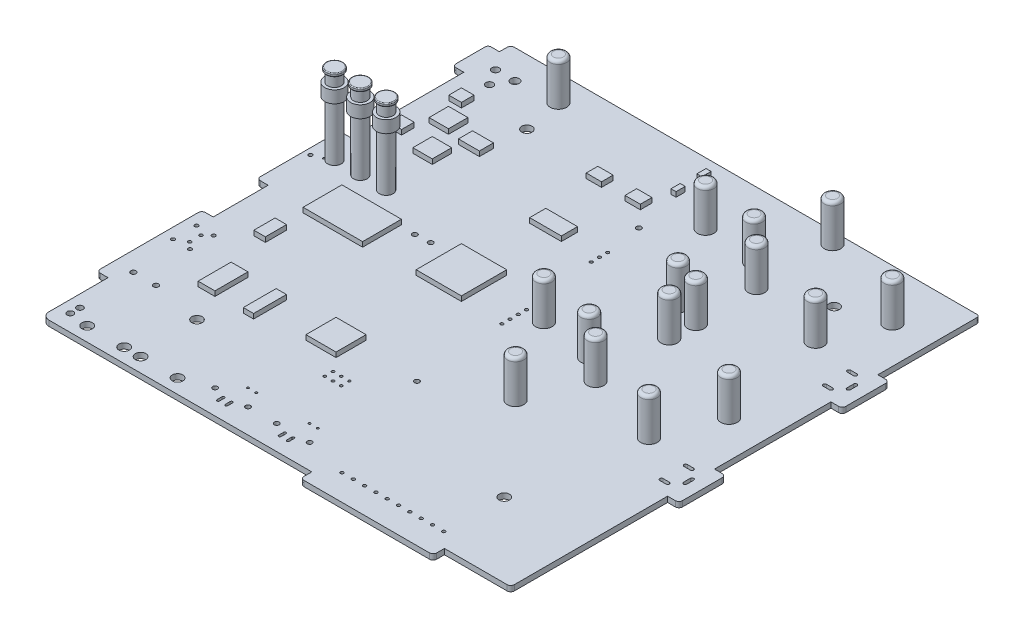
SolidWorks part; units mm, degrees
ref_plane "Front Plane" through (0, 0, 0) normal (0, 0, 1) x (1, 0, 0)
ref_plane "Top Plane" through (0, 0, 0) normal (0, 1, 0) x (1, 0, 0)
ref_plane "Right Plane" through (0, 0, 0) normal (1, 0, 0) x (0, 0, -1)
sketch "Sketch2"
sketch "Sketch3" plane through (0, 0, 0) normal (0, 1, 0) x (1, 0, 0)
  line L0 (-2.382, 130.5) -> (0, 130.5) construction
  line L1 (0, 130.5) -> (0, 95.5) construction
  line L2 (0, 95.5) -> (-2.382, 95.5) construction
  line L3 (-3.5, 94.382) -> (-3.5, 71.118) construction
  line L4 (-2.382, 70) -> (0, 70) construction
  line L5 (0, 70) -> (0, 53) construction
  line L6 (0, 53) -> (-2.382, 53) construction
  line L7 (-3.5, 51.882) -> (-3.5, 21.618) construction
  line L8 (-2.382, 20.5) -> (0, 20.5) construction
  line L9 (0, 20.5) -> (0, 2.2361) construction
  line L10 (83.5, 0) -> (2.2361, 0) construction
  line L11 (83.5, -2.382) -> (83.5, 0) construction
  line L12 (123.382, -3.5) -> (84.618, -3.5) construction
  line L13 (124.5, 0) -> (124.5, -2.382) construction
  line L14 (143.882, 0) -> (124.5, 0) construction
  line L15 (145, 48.5) -> (145, 1.118) construction
  line L16 (147.382, 48.5) -> (145, 48.5) construction
  line L17 (148.5, 61.882) -> (148.5, 49.618) construction
  line L18 (145, 63) -> (147.382, 63) construction
  line L19 (145, 99) -> (145, 63) construction
  line L20 (147.382, 99) -> (145, 99) construction
  line L21 (148.5, 112.382) -> (148.5, 100.118) construction
  line L22 (145, 113.5) -> (147.382, 113.5) construction
  line L23 (145, 144.0986) -> (145, 113.5) construction
  line L24 (144.0986, 145) -> (1.118, 145) construction
  line L25 (0, 143.882) -> (0, 141.5) construction
  line L26 (0, 141.5) -> (-2.5986, 141.5) construction
  line L27 (-3.5, 140.5986) -> (-3.5, 131.618) construction
  line L28 (-2.382, 130.5) -> (0, 130.5)
  line L29 (0, 130.5) -> (0, 95.5)
  line L30 (0, 95.5) -> (-2.382, 95.5)
  line L31 (-3.5, 94.382) -> (-3.5, 71.118)
  line L32 (-2.382, 70) -> (0, 70)
  line L33 (0, 70) -> (0, 53)
  line L34 (0, 53) -> (-2.382, 53)
  line L35 (-3.5, 51.882) -> (-3.5, 21.618)
  line L36 (-2.382, 20.5) -> (0, 20.5)
  line L37 (0, 20.5) -> (0, 2.2361)
  line L38 (83.5, 0) -> (2.2361, 0)
  line L39 (83.5, -2.382) -> (83.5, 0)
  line L40 (123.382, -3.5) -> (84.618, -3.5)
  line L41 (124.5, 0) -> (124.5, -2.382)
  line L42 (143.882, 0) -> (124.5, 0)
  line L43 (145, 48.5) -> (145, 1.118)
  line L44 (147.382, 48.5) -> (145, 48.5)
  line L45 (148.5, 61.882) -> (148.5, 49.618)
  line L46 (145, 63) -> (147.382, 63)
  line L47 (145, 99) -> (145, 63)
  line L48 (147.382, 99) -> (145, 99)
  line L49 (148.5, 112.382) -> (148.5, 100.118)
  line L50 (145, 113.5) -> (147.382, 113.5)
  line L51 (145, 144.0986) -> (145, 113.5)
  line L52 (144.0986, 145) -> (1.118, 145)
  line L53 (0, 143.882) -> (0, 141.5)
  line L54 (0, 141.5) -> (-2.5986, 141.5)
  line L55 (-3.5, 140.5986) -> (-3.5, 131.618)
  arc A0 (-3.5, 131.618) -> (-2.382, 130.5) centre (-2.382, 131.618) ccw construction
  arc A1 (-2.382, 95.5) -> (-3.5, 94.382) centre (-2.382, 94.382) ccw construction
  arc A2 (-3.5, 71.118) -> (-2.382, 70) centre (-2.382, 71.118) ccw construction
  arc A3 (-2.382, 53) -> (-3.5, 51.882) centre (-2.382, 51.882) ccw construction
  arc A4 (-3.5, 21.618) -> (-2.382, 20.5) centre (-2.382, 21.618) ccw construction
  arc A5 (0, 2.2361) -> (2.2361, 0) centre (2.2361, 2.2361) ccw construction
  arc A6 (83.5, -2.382) -> (84.618, -3.5) centre (84.618, -2.382) ccw construction
  arc A7 (123.382, -3.5) -> (124.5, -2.382) centre (123.382, -2.382) ccw construction
  arc A8 (143.882, 0) -> (145, 1.118) centre (143.882, 1.118) ccw construction
  arc A9 (147.382, 48.5) -> (148.5, 49.618) centre (147.382, 49.618) ccw construction
  arc A10 (148.5, 61.882) -> (147.382, 63) centre (147.382, 61.882) ccw construction
  arc A11 (147.382, 99) -> (148.5, 100.118) centre (147.382, 100.118) ccw construction
  arc A12 (148.5, 112.382) -> (147.382, 113.5) centre (147.382, 112.382) ccw construction
  arc A13 (145, 144.0986) -> (144.0986, 145) centre (144.0986, 144.0986) ccw construction
  arc A14 (1.118, 145) -> (0, 143.882) centre (1.118, 143.882) ccw construction
  arc A15 (-2.5986, 141.5) -> (-3.5, 140.5986) centre (-2.5986, 140.5986) ccw construction
  arc A16 (-3.5, 131.618) -> (-2.382, 130.5) centre (-2.382, 131.618) ccw
  arc A17 (-2.382, 95.5) -> (-3.5, 94.382) centre (-2.382, 94.382) ccw
  arc A18 (-3.5, 71.118) -> (-2.382, 70) centre (-2.382, 71.118) ccw
  arc A19 (-2.382, 53) -> (-3.5, 51.882) centre (-2.382, 51.882) ccw
  arc A20 (-3.5, 21.618) -> (-2.382, 20.5) centre (-2.382, 21.618) ccw
  arc A21 (0, 2.2361) -> (2.2361, 0) centre (2.2361, 2.2361) ccw
  arc A22 (83.5, -2.382) -> (84.618, -3.5) centre (84.618, -2.382) ccw
  arc A23 (123.382, -3.5) -> (124.5, -2.382) centre (123.382, -2.382) ccw
  arc A24 (143.882, 0) -> (145, 1.118) centre (143.882, 1.118) ccw
  arc A25 (147.382, 48.5) -> (148.5, 49.618) centre (147.382, 49.618) ccw
  arc A26 (148.5, 61.882) -> (147.382, 63) centre (147.382, 61.882) ccw
  arc A27 (147.382, 99) -> (148.5, 100.118) centre (147.382, 100.118) ccw
  arc A28 (148.5, 112.382) -> (147.382, 113.5) centre (147.382, 112.382) ccw
  arc A29 (145, 144.0986) -> (144.0986, 145) centre (144.0986, 144.0986) ccw
  arc A30 (1.118, 145) -> (0, 143.882) centre (1.118, 143.882) ccw
  arc A31 (-2.5986, 141.5) -> (-3.5, 140.5986) centre (-2.5986, 140.5986) ccw
  circle A32 centre (40.5, 79.75) radius 0.762 construction
  circle A33 centre (35.875, 79.5) radius 0.762 construction
  circle A34 centre (25, 23) radius 1.6 construction
  circle A35 centre (25, 125) radius 1.6 construction
  circle A36 centre (120, 125) radius 1.6 construction
  circle A37 centre (120, 23) radius 1.6 construction
  circle A38 centre (75.5, 40.5) radius 0.762 construction
  circle A39 centre (55.977, 35.0066) radius 0.5 construction
  circle A40 centre (65.0002, 30.1361) radius 0.381 construction
  circle A41 centre (75.275, 7.55) radius 0.75 construction
  circle A42 centre (72.735, 12.63) radius 0.3375 construction
  circle A43 centre (70.195, 12.63) radius 0.3375 construction
  circle A44 centre (65.115, 7.55) radius 0.75 construction
  circle A45 centre (53.685, 12.63) radius 0.3375 construction
  circle A46 centre (51.145, 12.63) radius 0.3375 construction
  circle A47 centre (56.225, 7.55) radius 0.75 construction
  circle A48 centre (46.065, 7.55) radius 0.75 construction
  circle A49 centre (37.592, 4.4) radius 1.6256 construction
  circle A50 centre (26.162, 4.4) radius 1.6256 construction
  circle A51 centre (21.082, 4.4) radius 1.6256 construction
  circle A52 centre (9.652, 4.4) radius 1.6256 construction
  circle A53 centre (3.7135, 5.121) radius 0.9652 construction
  circle A54 centre (3.7135, 8.0928) radius 0.9652 construction
  circle A55 centre (9.4624, 25.8572) radius 0.8 construction
  circle A56 centre (2.4624, 25.8572) radius 0.8 construction
  circle A57 centre (5.0334, 40.8053) radius 0.5625 construction
  circle A58 centre (3.0334, 42.7053) radius 0.5 construction
  circle A59 centre (-0.2666, 40.8053) radius 0.5625 construction
  circle A60 centre (5.0334, 48.1053) radius 0.5625 construction
  circle A61 centre (3.0334, 46.2053) radius 0.5 construction
  circle A62 centre (-0.2666, 48.1053) radius 0.5625 construction
  circle A63 centre (-1.5618, 84.65) radius 0.575 construction
  circle A64 centre (1.4382, 85.825) radius 0.3187 construction
  circle A65 centre (1.4382, 90.675) radius 0.3187 construction
  circle A66 centre (-1.5618, 91.85) radius 0.575 construction
  circle A67 centre (7.3, 131.15) radius 1.125 construction
  circle A68 centre (10.25, 136.05) radius 1.3125 construction
  circle A69 centre (4.25, 136.05) radius 1.125 construction
  circle A70 centre (40.5, 79.75) radius 0.762
  circle A71 centre (35.875, 79.5) radius 0.762
  circle A72 centre (25, 23) radius 1.6
  circle A73 centre (25, 125) radius 1.6
  circle A74 centre (120, 125) radius 1.6
  circle A75 centre (120, 23) radius 1.6
  circle A76 centre (75.5, 40.5) radius 0.762
  circle A77 centre (55.977, 35.0066) radius 0.5
  circle A78 centre (65.0002, 30.1361) radius 0.381
  circle A79 centre (75.275, 7.55) radius 0.75
  circle A80 centre (72.735, 12.63) radius 0.3375
  circle A81 centre (70.195, 12.63) radius 0.3375
  circle A82 centre (65.115, 7.55) radius 0.75
  circle A83 centre (53.685, 12.63) radius 0.3375
  circle A84 centre (51.145, 12.63) radius 0.3375
  circle A85 centre (56.225, 7.55) radius 0.75
  circle A86 centre (46.065, 7.55) radius 0.75
  circle A87 centre (37.592, 4.4) radius 1.6256
  circle A88 centre (26.162, 4.4) radius 1.6256
  circle A89 centre (21.082, 4.4) radius 1.6256
  circle A90 centre (9.652, 4.4) radius 1.6256
  circle A91 centre (3.7135, 5.121) radius 0.9652
  circle A92 centre (3.7135, 8.0928) radius 0.9652
  circle A93 centre (9.4624, 25.8572) radius 0.8
  circle A94 centre (2.4624, 25.8572) radius 0.8
  circle A95 centre (5.0334, 40.8053) radius 0.5625
  circle A96 centre (3.0334, 42.7053) radius 0.5
  circle A97 centre (-0.2666, 40.8053) radius 0.5625
  circle A98 centre (5.0334, 48.1053) radius 0.5625
  circle A99 centre (3.0334, 46.2053) radius 0.5
  circle A100 centre (-0.2666, 48.1053) radius 0.5625
  circle A101 centre (-1.5618, 84.65) radius 0.575
  circle A102 centre (1.4382, 85.825) radius 0.3187
  circle A103 centre (1.4382, 90.675) radius 0.3187
  circle A104 centre (-1.5618, 91.85) radius 0.575
  circle A105 centre (7.3, 131.15) radius 1.125
  circle A106 centre (10.25, 136.05) radius 1.3125
  circle A107 centre (4.25, 136.05) radius 1.125
extrude "Boss-Extrude1" add sketch "Sketch3" against normal blind 1.7
sketch "Sketch4" plane through (0, 0, 0) normal (0, 1, 0) x (1, 0, 0)
  line L0 (49.875, 6.223) -> (49.875, 4.699) construction
  line L1 (50.256, 6.223) -> (50.256, 4.699)
  line L2 (49.494, 6.223) -> (49.494, 4.699)
  line L3 (52.415, 6.223) -> (52.415, 4.699) construction
  line L4 (52.796, 6.223) -> (52.796, 4.699)
  line L5 (52.034, 6.223) -> (52.034, 4.699)
  line L6 (68.925, 6.223) -> (68.925, 4.699) construction
  line L7 (69.306, 6.223) -> (69.306, 4.699)
  line L8 (68.544, 6.223) -> (68.544, 4.699)
  line L9 (71.465, 6.223) -> (71.465, 4.699) construction
  line L10 (71.846, 6.223) -> (71.846, 4.699)
  line L11 (71.084, 6.223) -> (71.084, 4.699)
  line L12 (139.575, 59.5) -> (141.525, 59.5) construction
  line L13 (139.575, 60.025) -> (141.525, 60.025)
  line L14 (139.575, 58.975) -> (141.525, 58.975)
  line L15 (144.25, 56.8) -> (144.25, 54.7) construction
  line L16 (144.775, 56.8) -> (144.775, 54.7)
  line L17 (143.725, 56.8) -> (143.725, 54.7)
  line L18 (139.575, 52) -> (141.525, 52) construction
  line L19 (139.575, 52.525) -> (141.525, 52.525)
  line L20 (139.575, 51.475) -> (141.525, 51.475)
  line L21 (139.575, 110) -> (141.525, 110) construction
  line L22 (139.575, 110.525) -> (141.525, 110.525)
  line L23 (139.575, 109.475) -> (141.525, 109.475)
  line L24 (144.25, 107.3) -> (144.25, 105.2) construction
  line L25 (144.775, 107.3) -> (144.775, 105.2)
  line L26 (143.725, 107.3) -> (143.725, 105.2)
  line L27 (139.575, 102.5) -> (141.525, 102.5) construction
  line L28 (139.575, 103.025) -> (141.525, 103.025)
  line L29 (139.575, 101.975) -> (141.525, 101.975)
  circle A0 centre (62.4602, 30.1361) radius 0.4124
  circle A1 centre (59.9202, 30.1361) radius 0.4124
  circle A2 centre (59.9202, 27.5961) radius 0.4124
  circle A3 centre (62.4602, 27.5961) radius 0.4124
  circle A4 centre (65.0002, 27.5961) radius 0.4124
  circle A5 centre (88.3646, 4.4502) radius 0.4871
  circle A6 centre (91.8646, 4.4502) radius 0.4871
  circle A7 centre (95.3646, 4.4502) radius 0.4871
  circle A8 centre (98.8646, 4.4502) radius 0.4871
  circle A9 centre (102.3646, 4.4502) radius 0.4871
  circle A10 centre (105.8646, 4.4502) radius 0.4871
  circle A11 centre (109.3646, 4.4502) radius 0.4871
  circle A12 centre (112.8646, 4.4502) radius 0.4871
  circle A13 centre (116.3646, 4.4502) radius 0.4871
  circle A14 centre (119.8646, 4.4502) radius 0.4871
  arc A15 (50.256, 6.223) -> (49.494, 6.223) centre (49.875, 6.223) ccw
  arc A16 (49.494, 4.699) -> (50.256, 4.699) centre (49.875, 4.699) ccw
  arc A17 (52.796, 6.223) -> (52.034, 6.223) centre (52.415, 6.223) ccw
  arc A18 (52.034, 4.699) -> (52.796, 4.699) centre (52.415, 4.699) ccw
  arc A19 (69.306, 6.223) -> (68.544, 6.223) centre (68.925, 6.223) ccw
  arc A20 (68.544, 4.699) -> (69.306, 4.699) centre (68.925, 4.699) ccw
  arc A21 (71.846, 6.223) -> (71.084, 6.223) centre (71.465, 6.223) ccw
  arc A22 (71.084, 4.699) -> (71.846, 4.699) centre (71.465, 4.699) ccw
  arc A23 (71.846, 6.223) -> (71.084, 6.223) centre (71.465, 6.223) ccw construction
  arc A24 (139.575, 60.025) -> (139.575, 58.975) centre (139.575, 59.5) ccw
  arc A25 (141.525, 58.975) -> (141.525, 60.025) centre (141.525, 59.5) ccw
  arc A26 (144.775, 56.8) -> (143.725, 56.8) centre (144.25, 56.8) ccw
  arc A27 (143.725, 54.7) -> (144.775, 54.7) centre (144.25, 54.7) ccw
  arc A28 (139.575, 52.525) -> (139.575, 51.475) centre (139.575, 52) ccw
  arc A29 (141.525, 51.475) -> (141.525, 52.525) centre (141.525, 52) ccw
  arc A30 (139.575, 110.525) -> (139.575, 109.475) centre (139.575, 110) ccw
  arc A31 (141.525, 109.475) -> (141.525, 110.525) centre (141.525, 110) ccw
  arc A32 (144.775, 107.3) -> (143.725, 107.3) centre (144.25, 107.3) ccw
  arc A33 (143.725, 105.2) -> (144.775, 105.2) centre (144.25, 105.2) ccw
  arc A34 (139.575, 103.025) -> (139.575, 101.975) centre (139.575, 102.5) ccw
  arc A35 (141.525, 101.975) -> (141.525, 103.025) centre (141.525, 102.5) ccw
  arc A36 (144.775, 56.8) -> (143.725, 56.8) centre (144.25, 56.8) ccw construction
  circle A37 centre (73.25, 81.7) radius 0.4699 construction
  circle A38 centre (73.25, 79.16) radius 0.4699 construction
  circle A39 centre (73.25, 76.62) radius 0.4699 construction
  circle A40 centre (73.25, 74.08) radius 0.4699 construction
  circle A41 centre (73.25, 71.54) radius 0.4699 construction
  circle A42 centre (73.25, 69) radius 0.4699 construction
  circle A43 centre (73.25, 81.7) radius 0.4699
  circle A44 centre (73.25, 79.16) radius 0.4699
  circle A45 centre (73.25, 76.62) radius 0.4699
  circle A46 centre (73.25, 74.08) radius 0.4699
  circle A47 centre (73.25, 71.54) radius 0.4699
  circle A48 centre (73.25, 69) radius 0.4699
  circle A49 centre (128.016, 112.25) radius 0.3175 construction
  circle A50 centre (134, 127.984) radius 0.3175 construction
  circle A51 centre (103.5, 139.984) radius 0.3175 construction
  circle A52 centre (103.5, 116.484) radius 0.3175 construction
  circle A53 centre (79.75, 124.484) radius 0.3175 construction
  circle A54 centre (70.5, 99.38) radius 0.4699 construction
  circle A55 centre (70.5, 101.92) radius 0.4699 construction
  circle A56 centre (59.706, 104.528) radius 0.2231 construction
  circle A57 centre (70.5, 104.46) radius 0.4699 construction
  circle A58 centre (68.75, 115.875) radius 0.762 construction
  circle A59 centre (128.016, 112.25) radius 0.3175
  circle A60 centre (134, 127.984) radius 0.3175
  circle A61 centre (103.5, 139.984) radius 0.3175
  circle A62 centre (103.5, 116.484) radius 0.3175
  circle A63 centre (79.75, 124.484) radius 0.3175
  circle A64 centre (70.5, 99.38) radius 0.4699
  circle A65 centre (70.5, 101.92) radius 0.4699
  circle A66 centre (59.706, 104.528) radius 0.2231
  circle A67 centre (70.5, 104.46) radius 0.4699
  circle A68 centre (68.75, 115.875) radius 0.762
  point P77 (49.875, 5.461)
  point P84 (52.415, 5.461)
  point P93 (68.925, 5.461)
  point P102 (71.465, 5.461)
  point P118 (140.55, 59.5)
  point P123 (144.25, 55.75)
  point P132 (140.55, 52)
  point P141 (140.55, 110)
  point P150 (144.25, 106.25)
  point P159 (140.55, 102.5)
extrude "Cut-Extrude1" cut sketch "Sketch4" against normal through all
sketch "Sketch6" plane through (0, 0, 0) normal (0, 1, 0) x (1, 0, 0)
  circle A0 centre (96.25, 50.25) radius 2.54 construction
  circle A1 centre (79.75, 75.5) radius 2.54 construction
  circle A2 centre (96.25, 73) radius 2.54 construction
  circle A3 centre (103.5, 67.75) radius 2.54 construction
  circle A4 centre (127, 60.75) radius 2.54 construction
  circle A5 centre (134, 78.5) radius 2.54 construction
  circle A6 centre (103.5, 90.5) radius 2.54 construction
  circle A7 centre (103.75, 98.5) radius 2.54 construction
  circle A8 centre (96.25, 100.5) radius 2.54 construction
  circle A9 centre (134, 129) radius 2.54 construction
  circle A10 centre (127, 112.25) radius 2.54 construction
  circle A11 centre (103.5, 117.5) radius 2.54 construction
  circle A12 centre (96.25, 124) radius 2.54 construction
  circle A13 centre (103.5, 141) radius 2.54 construction
  circle A14 centre (79.75, 125.5) radius 2.54 construction
  circle A15 centre (23.25, 136.5) radius 2.54 construction
  circle A16 centre (96.25, 50.25) radius 2.54
  circle A17 centre (79.75, 75.5) radius 2.54
  circle A18 centre (96.25, 73) radius 2.54
  circle A19 centre (103.5, 67.75) radius 2.54
  circle A20 centre (127, 60.75) radius 2.54
  circle A21 centre (134, 78.5) radius 2.54
  circle A22 centre (103.5, 90.5) radius 2.54
  circle A23 centre (103.75, 98.5) radius 2.54
  circle A24 centre (96.25, 100.5) radius 2.54
  circle A25 centre (134, 129) radius 2.54
  circle A26 centre (127, 112.25) radius 2.54
  circle A27 centre (103.5, 117.5) radius 2.54
  circle A28 centre (96.25, 124) radius 2.54
  circle A29 centre (103.5, 141) radius 2.54
  circle A30 centre (79.75, 125.5) radius 2.54
  circle A31 centre (23.25, 136.5) radius 2.54
extrude "Boss-Extrude2" add sketch "Sketch6" along normal blind 13 from offset 0.5 separate body
fillet "Fillet1" radius 1 1 edges at (23.25, 13.5, -133.96)
fillet "Fillet2" radius 1 1 edges at (79.75, 13.5, -122.96)
fillet "Fillet3" radius 1 1 edges at (103.5, 13.5, -138.46)
fillet "Fillet4" radius 1 1 edges at (134, 13.5, -126.46)
fillet "Fillet5" radius 1 1 edges at (96.25, 13.5, -121.46)
fillet "Fillet6" radius 1 1 edges at (103.5, 13.5, -114.96)
fillet "Fillet7" radius 1 1 edges at (127, 13.5, -109.71)
fillet "Fillet8" radius 1 1 edges at (96.25, 13.5, -97.96)
fillet "Fillet9" radius 1 1 edges at (103.75, 13.5, -95.96)
fillet "Fillet10" radius 1 1 edges at (103.5, 13.5, -87.96)
fillet "Fillet11" radius 1 1 edges at (134, 13.5, -75.96)
fillet "Fillet12" radius 1 1 edges at (79.75, 13.5, -72.96)
fillet "Fillet13" radius 1 1 edges at (96.25, 13.5, -70.46)
fillet "Fillet14" radius 1 1 edges at (103.5, 13.5, -65.21)
fillet "Fillet15" radius 1 1 edges at (127, 13.5, -58.21)
fillet "Fillet16" radius 1 1 edges at (96.25, 13.5, -47.71)
sketch "Sketch7" plane through (0, 0, 0) normal (0, 1, 0) x (1, 0, 0)
  line L0 (60.75, 68.75) -> (47.75, 68.75) construction
  line L1 (12.8, 80) -> (31.2, 80)
  line L2 (12.8, 80) -> (12.8, 68)
  line L3 (12.8, 68) -> (31.2, 68)
  line L4 (31.2, 80) -> (31.2, 68)
  line L5 (47, 82.75) -> (61, 82.75)
  line L6 (47, 82.75) -> (47, 68.75)
  line L8 (61, 82.75) -> (61, 68.75)
  line L9 (61, 68.75) -> (47, 68.75)
  line L10 (56.652, 34.3316) -> (47.352, 34.3316) construction
  line L11 (56.652, 43.6316) -> (56.652, 34.3316) construction
  line L12 (47.352, 34.3316) -> (47.352, 43.6316) construction
  line L13 (47.352, 43.6316) -> (56.652, 43.6316) construction
  line L14 (56.652, 34.3316) -> (47.352, 34.3316)
  line L15 (56.652, 43.6316) -> (56.652, 34.3316)
  line L16 (47.352, 34.3316) -> (47.352, 43.6316)
  line L17 (47.352, 43.6316) -> (56.652, 43.6316)
  line L18 (16.3548, 31.9893) -> (21.5548, 31.9893) construction
  line L19 (21.5548, 31.9893) -> (21.5548, 42.1893) construction
  line L20 (21.5548, 42.1893) -> (16.3548, 42.1893) construction
  line L21 (16.3548, 42.1893) -> (16.3548, 31.9893) construction
  line L22 (16.3548, 31.9893) -> (21.5548, 31.9893)
  line L23 (21.5548, 31.9893) -> (21.5548, 42.1893)
  line L24 (21.5548, 42.1893) -> (16.3548, 42.1893)
  line L25 (16.3548, 42.1893) -> (16.3548, 31.9893)
  line L26 (64.719, 137.828) -> (64.719, 140.673) construction
  line L27 (66.281, 137.828) -> (64.719, 137.828) construction
  line L28 (66.281, 140.673) -> (66.281, 137.828) construction
  line L29 (64.719, 140.673) -> (66.281, 140.673) construction
  line L30 (64.719, 129.828) -> (64.719, 132.673) construction
  line L31 (66.281, 129.828) -> (64.719, 129.828) construction
  line L32 (66.281, 132.673) -> (66.281, 129.828) construction
  line L33 (64.719, 132.673) -> (66.281, 132.673) construction
  line L34 (59.388, 120.947) -> (64.112, 120.947) construction
  line L35 (64.112, 120.947) -> (64.112, 124.553) construction
  line L36 (64.112, 124.553) -> (59.388, 124.553) construction
  line L37 (59.388, 124.553) -> (59.388, 120.947) construction
  line L38 (47.388, 124.553) -> (47.388, 120.947) construction
  line L39 (47.388, 120.947) -> (52.112, 120.947) construction
  line L40 (52.112, 120.947) -> (52.112, 124.553) construction
  line L41 (52.112, 124.553) -> (47.388, 124.553) construction
  line L42 (64.719, 137.828) -> (64.719, 140.673)
  line L43 (66.281, 137.828) -> (64.719, 137.828)
  line L44 (66.281, 140.673) -> (66.281, 137.828)
  line L45 (64.719, 140.673) -> (66.281, 140.673)
  line L46 (64.719, 129.828) -> (64.719, 132.673)
  line L47 (66.281, 129.828) -> (64.719, 129.828)
  line L48 (66.281, 132.673) -> (66.281, 129.828)
  line L49 (64.719, 132.673) -> (66.281, 132.673)
  line L50 (59.388, 120.947) -> (64.112, 120.947)
  line L51 (64.112, 120.947) -> (64.112, 124.553)
  line L52 (64.112, 124.553) -> (59.388, 124.553)
  line L53 (59.388, 124.553) -> (59.388, 120.947)
  line L54 (47.388, 124.553) -> (47.388, 120.947)
  line L55 (47.388, 120.947) -> (52.112, 120.947)
  line L56 (52.112, 120.947) -> (52.112, 124.553)
  line L57 (52.112, 124.553) -> (47.388, 124.553)
  line L58 (14.888, 54.253) -> (11.332, 54.253) construction
  line L59 (11.332, 54.253) -> (11.332, 60.807) construction
  line L60 (14.888, 60.807) -> (14.888, 54.253) construction
  line L61 (11.332, 60.807) -> (14.888, 60.807) construction
  line L62 (14.888, 54.253) -> (11.332, 54.253)
  line L63 (11.332, 54.253) -> (11.332, 60.807)
  line L64 (14.888, 60.807) -> (14.888, 54.253)
  line L65 (11.332, 60.807) -> (14.888, 60.807)
  line L66 (24.99, 114.675) -> (24.99, 110.325) construction
  line L67 (30.4108, 42.072) -> (33.5858, 42.072)
  line L68 (30.4108, 42.072) -> (30.4108, 31.912)
  line L69 (30.4108, 31.912) -> (33.5858, 31.912)
  line L70 (33.5858, 42.072) -> (33.5858, 31.912)
  line L71 (50.6, 105.25) -> (60.4, 105.25)
  line L72 (50.6, 105.25) -> (50.6, 100.25)
  line L73 (50.6, 100.25) -> (60.4, 100.25)
  line L74 (60.4, 105.25) -> (60.4, 100.25)
  line L75 (18.51, 110.325) -> (24.99, 110.325) construction
  line L76 (18.51, 110.325) -> (18.51, 114.675) construction
  line L77 (24.99, 114.675) -> (18.51, 114.675) construction
  line L78 (24.99, 114.675) -> (24.99, 110.325)
  line L79 (18.51, 110.325) -> (24.99, 110.325)
  line L80 (18.51, 110.325) -> (18.51, 114.675)
  line L81 (24.99, 114.675) -> (18.51, 114.675)
  line L82 (5.3, 124.45) -> (5.3, 120.55) construction
  line L83 (9.2, 124.45) -> (5.3, 124.45) construction
  line L84 (9.2, 124.45) -> (9.2, 120.55) construction
  line L85 (9.2, 120.55) -> (5.3, 120.55) construction
  line L86 (8.25, 111.5) -> (8.25, 117.5) construction
  line L87 (14.25, 117.5) -> (8.25, 117.5) construction
  line L88 (14.25, 111.5) -> (14.25, 117.5) construction
  line L89 (14.25, 111.5) -> (8.25, 111.5) construction
  line L90 (19.816, 100.9248) -> (13.816, 100.9248) construction
  line L91 (19.816, 106.9248) -> (19.816, 100.9248) construction
  line L92 (19.816, 106.9248) -> (13.816, 106.9248) construction
  line L93 (13.816, 106.9248) -> (13.816, 100.9248) construction
  line L94 (7.2, 107.95) -> (7.2, 104.05) construction
  line L95 (3.3, 104.05) -> (7.2, 104.05) construction
  line L96 (3.3, 107.95) -> (3.3, 104.05) construction
  line L97 (3.3, 107.95) -> (7.2, 107.95) construction
  line L98 (5.3, 124.45) -> (5.3, 120.55)
  line L99 (9.2, 124.45) -> (5.3, 124.45)
  line L100 (9.2, 124.45) -> (9.2, 120.55)
  line L101 (9.2, 120.55) -> (5.3, 120.55)
  line L102 (8.25, 111.5) -> (8.25, 117.5)
  line L103 (14.25, 117.5) -> (8.25, 117.5)
  line L104 (14.25, 111.5) -> (14.25, 117.5)
  line L105 (14.25, 111.5) -> (8.25, 111.5)
  line L106 (19.816, 100.9248) -> (13.816, 100.9248)
  line L107 (19.816, 106.9248) -> (19.816, 100.9248)
  line L108 (19.816, 106.9248) -> (13.816, 106.9248)
  line L109 (13.816, 106.9248) -> (13.816, 100.9248)
  line L110 (7.2, 107.95) -> (7.2, 104.05)
  line L111 (3.3, 104.05) -> (7.2, 104.05)
  line L112 (3.3, 107.95) -> (3.3, 104.05)
  line L113 (3.3, 107.95) -> (7.2, 107.95)
extrude "Boss-Extrude3" add sketch "Sketch7" along normal blind 1.5 separate body
sketch "Sketch8" plane through (0, 0, 0) normal (0, 1, 0) x (1, 0, 0)
  line L0 (-3.3666, 44.4553) -> (7.2529, 44.4553)
  line L1 (-3.3666, 48.9553) -> (-3.3666, 39.9553) construction
  line L2 (144.25, 55.75) -> (149.1729, 55.75)
  line L3 (144.25, 56.8) -> (144.25, 54.7) construction
  line L4 (144.25, 106.25) -> (150.2294, 106.25)
  line L5 (144.25, 107.3) -> (144.25, 105.2) construction
  line L6 (0.425, 76.375) -> (-5.5368, 76.375)
  line L7 (0.425, 74.625) -> (0.425, 78.125) construction
sketch "Sketch9" plane through (0, 0, 0) normal (0, 1, 0) x (1, 0, 0)
  circle A0 centre (6.5, 84.002) radius 2.1
  circle A1 centre (14.5, 84.002) radius 2.1
  circle A2 centre (22.5, 84.002) radius 2.1
  dimension "D1" = 4.2
extrude "Boss-Extrude4" add sketch "Sketch9" along normal blind 25 from offset 3 separate body
ref_plane "Plane1" through (0, 23.9, 0) normal (0, 1, 0) x (1, 0, 0)
sketch "Sketch10" plane through (0, 23.9, 0) normal (0, 1, 0) x (1, 0, 0)
  circle A0 centre (6.5, 84.002) radius 3
  circle A1 centre (14.5, 84.002) radius 3
  circle A2 centre (22.5, 84.002) radius 3
  circle A4 centre (22.5, 84.002) radius 2.1
  circle A5 centre (22.5, 84.002) radius 2.1
  circle A6 centre (14.5, 84.002) radius 2.1
  circle A7 centre (14.5, 84.002) radius 2.1
  circle A8 centre (6.5, 84.002) radius 2.1
  circle A9 centre (6.5, 84.002) radius 2.1
  dimension "D4" = 6
  dimension "D1" = 0
  dimension "D2" = 0
  dimension "D3" = 0
extrude "Boss-Extrude5" add sketch "Sketch10" against normal blind 3.75 separate body
sketch "Sketch11" plane through (0, 28, 0) normal (0, 1, 0) x (1, 0, 0)
  circle A0 centre (14.5, 84.002) radius 2.1 construction
  circle A1 centre (22.5, 84.002) radius 2.1 construction
  circle A2 centre (6.5, 84.002) radius 2.6
  circle A3 centre (6.5, 84.002) radius 2.6
  circle A6 centre (14.5, 84.002) radius 2.6
  circle A9 centre (22.5, 84.002) radius 2.6
  dimension "D1" = 0.5
extrude "Boss-Extrude6" add sketch "Sketch11" against normal blind 1
fillet "Fillet17" radius 0.25 2 edges at (6.5, 28, -81.402) (6.5, 27, -81.402)
fillet "Fillet18" radius 0.25 2 edges at (14.5, 27, -81.402) (14.5, 28, -81.402)
fillet "Fillet19" radius 0.25 2 edges at (22.5, 28, -81.402) (22.5, 27, -81.402)
